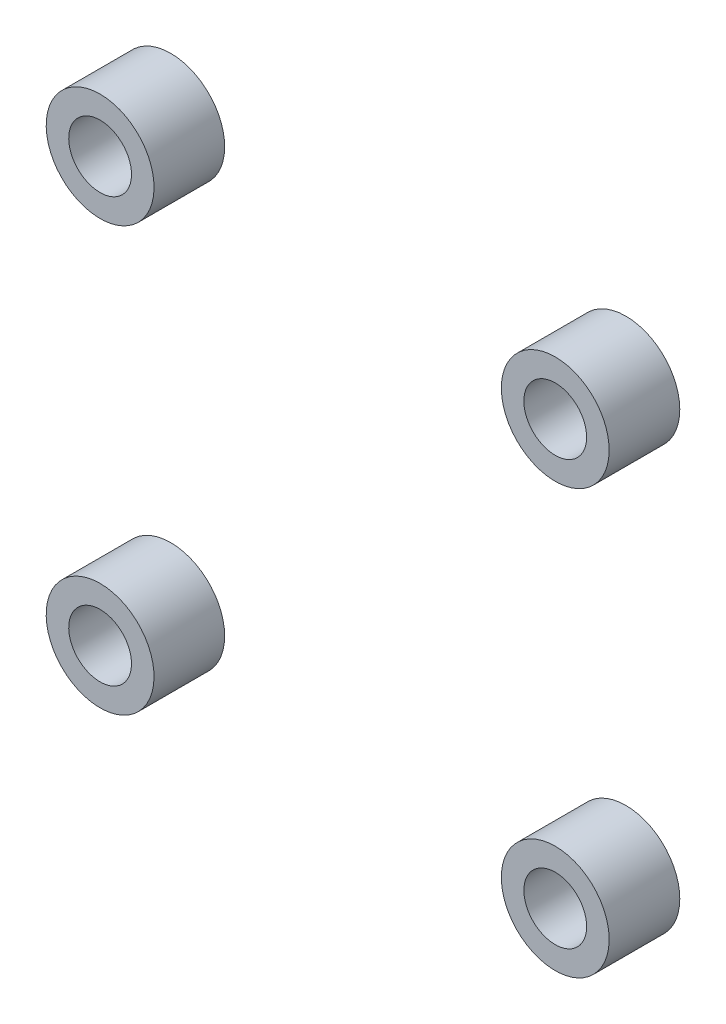
SolidWorks part; units mm, degrees
ref_plane "Front Plane" through (0, 0, 0) normal (0, 0, 1) x (1, 0, 0)
ref_plane "Top Plane" through (0, 0, 0) normal (0, 1, 0) x (1, 0, 0)
ref_plane "Right Plane" through (0, 0, 0) normal (1, 0, 0) x (0, 0, -1)
sketch "Sketch1" plane through (0, 0, 0) normal (0, 0, 1) x (1, 0, 0)
  circle A0 centre (-14.5, 13.5) radius 2
  circle A1 centre (-14.5, 13.5) radius 3.4355
  arc A2 (-16.2, 13.5) -> (-12.8, 13.5) centre (-14.5, 13.5) ccw construction
  circle A3 centre (14.5, 13.5) radius 2
  circle A4 centre (14.5, 13.5) radius 3.4355
  circle A5 centre (14.5, -13.5) radius 2
  circle A6 centre (14.5, -13.5) radius 3.4355
  circle A7 centre (-14.5, -13.5) radius 2
  circle A8 centre (-14.5, -13.5) radius 3.4355
  arc A9 (-16.2, -13.5) -> (-12.8, -13.5) centre (-14.5, -13.5) ccw construction
  arc A10 (12.8, 13.5) -> (16.2, 13.5) centre (14.5, 13.5) ccw construction
  dimension "D1" = 0.3
  dimension "D2" = 1.4355
  dimension "D3" = 2
  dimension "D4" = 2
extrude "Boss-Extrude1" add sketch "Sketch1" along normal up to surface (4.5 mm away)
